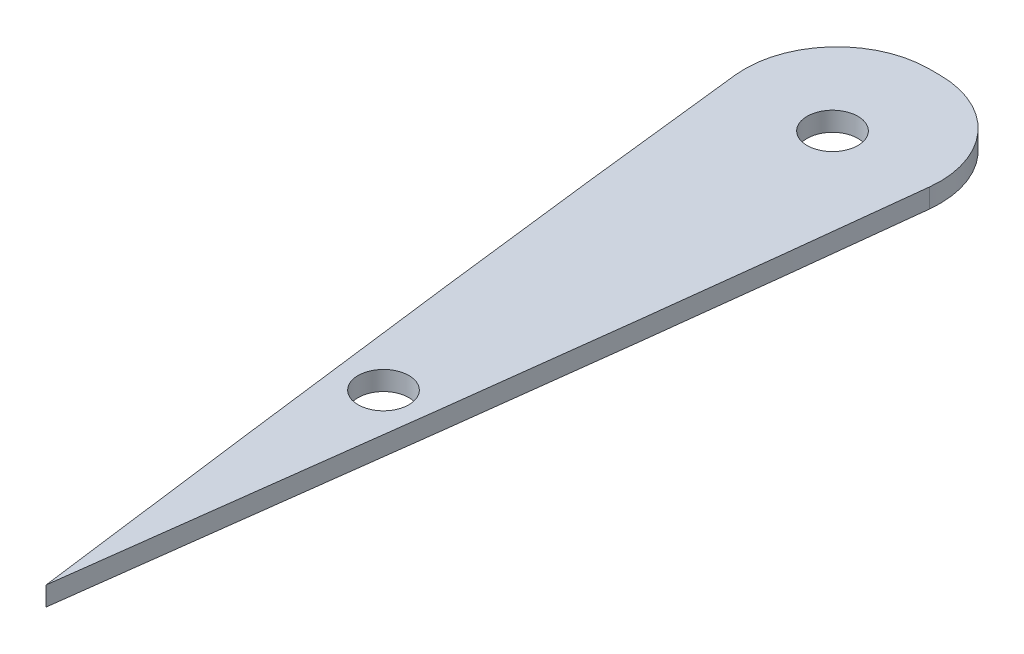
SolidWorks part; units mm, degrees
material "Balsa"
ref_plane "Front Plane" through (0, 0, 0) normal (0, 0, 1) x (1, 0, 0)
ref_plane "Top Plane" through (0, 0, 0) normal (0, 1, 0) x (1, 0, 0)
ref_plane "Right Plane" through (0, 0, 0) normal (1, 0, 0) x (0, 0, -1)
sketch "Sketch1" plane through (0, 0, 0) normal (0, 1, 0) x (1, 0, 0)
  line L0 (1.1081, 1.7265) -> (-45.0799, 1.7265) construction
  line L1 (-45.0799, 1.7265) -> (-45.0799, -11.2275) construction
  line L2 (-45.0799, -11.2275) -> (43.7517, -11.2275) construction
  line L3 (1.1081, 103.3269) -> (1.1081, -99.8738) construction
  line L4 (-45.0799, -11.2275) -> (-45.0799, -20.7525) construction
  line L5 (-28.2049, 1.7265) -> (-28.2049, -3.6075) construction
  line L6 (-9.9553, -3.6075) -> (-6.7697, -3.6075)
  line L7 (-28.2049, -3.6075) -> (-9.9553, -3.6075) construction
  line L8 (-6.7697, -3.6075) -> (1.1081, -3.6075) construction
  line L9 (8.9859, -3.6075) -> (12.1715, -3.6075)
  line L10 (12.1715, -3.6075) -> (18.1346, -3.6075) construction
  line L11 (12.1715, -3.6075) -> (18.1346, -3.6075) construction
  line L12 (18.1346, -3.6075) -> (29.3788, -3.6075) construction
  line L13 (1.1081, -3.6075) -> (8.9859, -3.6075) construction
  line L14 (-6.7697, -3.6075) -> (8.9859, -3.6075)
  circle A0 centre (1.1081, -11.3265) radius 1.9844 construction
  circle A1 centre (1.1081, -11.3265) radius 1.9844
  spline S0 degree 3 poles (1.1081, -99.8738) (4.5273, -73.5318) (7.9866, -47.1872) (10.6029, -20.7525) knots 0 0 0 0 0.38497 0.38497 0.38497 0.38497
  spline S3 degree 3 poles (1.1081, -99.8738) (-2.3112, -73.5318) (-5.7704, -47.1872) (-8.3867, -20.7525) knots 0 0 0 0 0.38497 0.38497 0.38497 0.38497
  spline S4 degree 3 poles (10.6029, -20.7525) (11.1, -15.7302) (11.6306, -10.016) (12.114, -4.2968) (12.1715, -3.6075) knots 0.38497 0.38497 0.38497 0.38497 0.458109 0.468132 0.468132 0.468132 0.468132
  spline S5 degree 3 poles (-8.3867, -20.7525) (-8.8838, -15.7302) (-9.4144, -10.016) (-9.8978, -4.2968) (-9.9553, -3.6075) knots 0.38497 0.38497 0.38497 0.38497 0.458109 0.468132 0.468132 0.468132 0.468132
  spline S8 degree 3 poles (12.1715, -3.6075) (12.8364, 4.367) (14.1908, 23.6726) (14.0058, 48.0803) (13.0188, 67.5796) (11.3266, 78.9472) (9.5869, 86.9693) (8.1237, 93.6397) (6.4505, 97.563) (4.8164, 101.3994) (2.3437, 102.5279) (1.1081, 103.3269) knots 0.468132 0.468132 0.468132 0.468132 0.584075 0.748482 0.821537 0.866809 0.914778 0.94069 0.965303 0.976863 1 1 1 1 construction
  spline S9 degree 3 poles (1.1081, 99.6196) (1.2739, 99.518) (1.6209, 99.2976) (2.0134, 99.0137) (2.3095, 98.7539) (2.4667, 98.5788) (2.6076, 98.3713) (2.8163, 97.9774) (3.0534, 97.4394) (3.4327, 96.5453) (3.8774, 95.496) (4.541, 93.8448) (5.2023, 91.9048) (5.8236, 89.3366) (6.4213, 86.5662) (7.0145, 83.8293) (7.767, 80.1951) (8.6007, 75.6781) (9.6391, 68.4081) (10.3034, 59.2354) (10.6788, 47.9926) (10.8555, 36.7918) (10.7415, 25.5951) (10.3009, 14.4244) (9.6564, 4.6878) (9.1767, -1.3266) (8.9859, -3.6075) knots 0.118744 0.118744 0.118744 0.118744 0.122149 0.125554 0.12896 0.132365 0.13577 0.139175 0.142581 0.145986 0.152796 0.159607 0.173228 0.186849 0.20047 0.214091 0.227711 0.254953 0.282195 0.336679 0.391163 0.445646 0.50013 0.554614 0.609098 0.642376 0.642376 0.642376 0.642376 construction
  spline S10 degree 3 poles (-7.1984, 1.7265) (-7.237, 2.2289) (-7.5577, 6.4638) (-8.0847, 14.4244) (-8.5253, 25.5951) (-8.6393, 36.7918) (-8.4626, 47.9926) (-8.0872, 59.2354) (-7.4229, 68.4081) (-6.3845, 75.6781) (-5.5508, 80.1951) (-4.7983, 83.8293) (-4.2051, 86.5662) (-3.6074, 89.3366) (-2.9861, 91.9048) (-2.3248, 93.8448) (-1.6612, 95.496) (-1.2165, 96.5453) (-0.8372, 97.4394) (-0.6001, 97.9774) (-0.3914, 98.3713) (-0.2505, 98.5788) (-0.0933, 98.7539) (0.2028, 99.0137) (0.5953, 99.2976) (0.9423, 99.518) (1.1081, 99.6196) knots 0.492798 0.492798 0.492798 0.492798 0.50013 0.554614 0.609098 0.663581 0.718065 0.772549 0.827033 0.854275 0.881516 0.895137 0.908758 0.922379 0.936 0.949621 0.956432 0.963242 0.966647 0.970053 0.973458 0.976863 0.980268 0.983674 0.987079 0.990484 0.990484 0.990484 0.990484 construction
  spline S11 degree 3 poles (-10.3826, 1.7265) (-10.8572, 7.9268) (-11.9611, 25.4575) (-11.7896, 48.0803) (-10.8026, 67.5796) (-9.1104, 78.9472) (-7.3707, 86.9693) (-5.9075, 93.6397) (-4.2343, 97.563) (-2.6002, 101.3994) (-0.1276, 102.5279) (1.1081, 103.3269) knots 0.493976 0.493976 0.493976 0.493976 0.584075 0.748482 0.821537 0.866809 0.914778 0.94069 0.965303 0.976863 1 1 1 1 construction
  spline S12 degree 3 poles (-9.9553, -3.6075) (-10.1035, -1.8299) (-10.2465, -0.0519) (-10.3826, 1.7265) knots 0.468132 0.468132 0.468132 0.468132 0.493976 0.493976 0.493976 0.493976 construction
  spline S13 degree 3 poles (-6.7697, -3.6075) (-6.9185, -1.8292) (-7.0618, -0.0511) (-7.1984, 1.7265) knots 0.466852 0.466852 0.466852 0.466852 0.492798 0.492798 0.492798 0.492798 construction
  dimension "D4" = 3.9688
  dimension "D1" = 12.954
  dimension "D2" = 9.525
  dimension "D3" = 5.334
extrude "Boss-Extrude1" add sketch "Sketch1" along normal blind 169.8727
sketch "Sketch2" plane through (0, 169.8727, 0) normal (0, 1, 0) x (1, 0, 0)
  line L1 (-9.9553, -3.6075) -> (25.8085, -3.6075)
  line L2 (-9.9553, -3.6075) -> (-9.9553, -26.3125)
  line L3 (-9.9553, -26.3125) -> (25.8085, -26.3125)
  line L4 (25.8085, -3.6075) -> (25.8085, -26.3125)
  circle A0 centre (1.1081, -11.3265) radius 1.9844 construction
  dimension "D1" = 14.986
extrude "Cut-Extrude1" cut sketch "Sketch2" against normal blind 23.0581
extrude "Cut-Extrude2" cut sketch "Sketch2<2>" along normal blind 23.0581 from surface starting at face at (-1.1046, 0, 29.7187)
sketch "Sketch2<2>" plane through (0, 169.8727, 0) normal (0, 1, 0) x (1, 0, 0) same geometry as "Sketch2"
fillet "Fillet1" radius 7.62 6 edges at (-7.8242, 11.5291, 26.3125) (10.0403, 11.5291, 26.3125) (12.1715, 84.9363, 3.6075) (-7.8242, 158.3436, 26.3125) (10.0403, 158.3436, 26.3125)
sketch "Sketch6" plane through (0, 0, 0) normal (0, -1, 0) x (1, 0, 0)
  line L0 (1.1081, 3.6075) -> (1.1081, 99.8738) construction
  line L1 (-1.6395, 3.6075) -> (3.8557, 3.6075) construction
  line L2 (-6.9254, 34.7606) -> (9.1416, 34.7606) construction
  circle A0 centre (1.1081, 71.9338) radius 2.1
  circle A1 centre (1.1081, 34.7606) radius 2.1
  dimension "D1" = 4.2
  dimension "D2" = 27.94
extrude "Cut-Extrude3" cut sketch "Sketch6" against normal through all both and the other way through all
sketch "Sketch7" plane through (0, 0, 0) normal (1, 0, 0) x (0, 0, -1)
  line L0 (-3.6075, 146.8145) -> (-3.6075, 23.0581) construction
  line L1 (-99.8738, 0) -> (-3.6075, 0)
  line L2 (-99.8738, 0) -> (-99.8738, 159.2848)
  line L3 (-99.8738, 159.2848) -> (-3.6075, 159.2848)
  line L4 (-3.6075, 0) -> (-3.6075, 159.2848)
  line L6 (-99.8738, 169.8727) -> (-3.6075, 169.8727)
  line L7 (-99.8738, 169.8727) -> (-99.8738, 160.8723)
  line L8 (-99.8738, 160.8723) -> (-3.6075, 160.8723)
  line L9 (-3.6075, 169.8727) -> (-3.6075, 160.8723)
  dimension "D2" = 1.5875
extrude "Cut-Extrude4" cut sketch "Sketch7" against normal through all both and the other way through all
